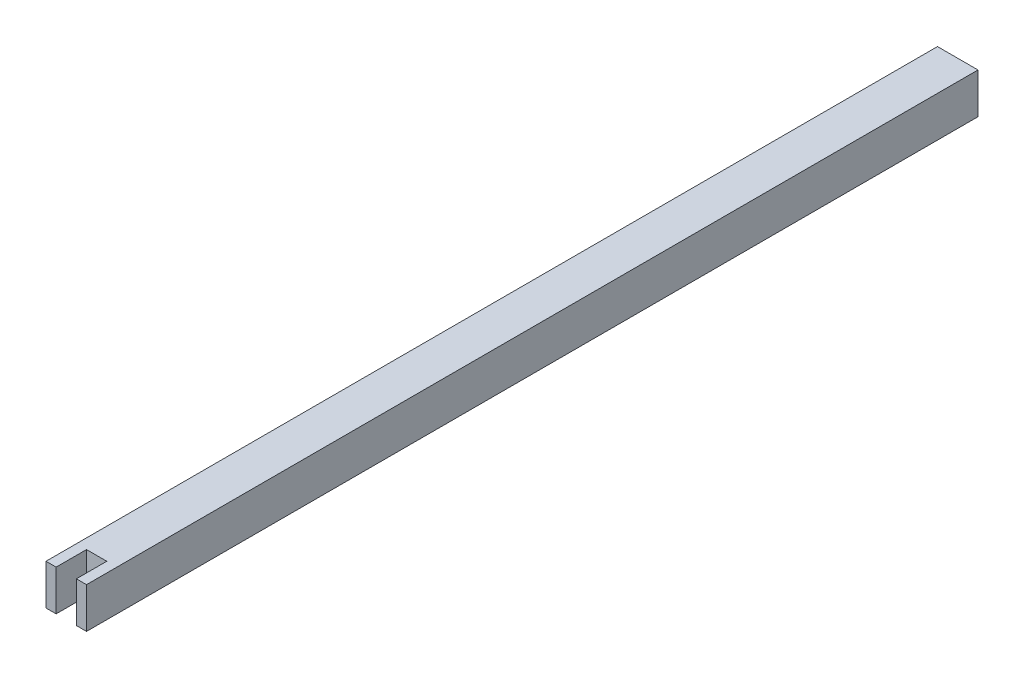
SolidWorks part; units mm, degrees
ref_plane "Front" through (0, 0, 0) normal (0, 0, 1) x (1, 0, 0)
ref_plane "Top" through (0, 0, 0) normal (0, 1, 0) x (1, 0, 0)
ref_plane "Right" through (0, 0, 0) normal (1, 0, 0) x (0, 0, -1)
sketch "Esquisse1" plane through (0, 0, 0) normal (0, 0, 1) x (1, 0, 0)
  line L1 (0, 0) -> (100, 0)
  line L2 (0, 0) -> (0, 100)
  line L3 (0, 100) -> (100, 100)
  line L4 (100, 0) -> (100, 100)
  dimension "D1" = 100
  dimension "D2" = 100
extrude "Boss.-Extru.1" add sketch "Esquisse1" along normal blind 2200
sketch "Esquisse2" plane through (0, 0, 0) normal (0, -1, 0) x (1, 0, 0)
  line L0 (0, 2200) -> (100, 2200) construction
  line L1 (25, 2200) -> (75, 2200)
  line L2 (25, 2200) -> (25, 2125)
  line L3 (25, 2125) -> (75, 2125)
  line L4 (75, 2200) -> (75, 2125)
  line L5 (50, 2125) -> (50, 2200) construction
  dimension "D1" = 50
  dimension "D2" = 75
extrude "Enlèv. mat.-Extru.1" cut sketch "Esquisse2" against normal through all
